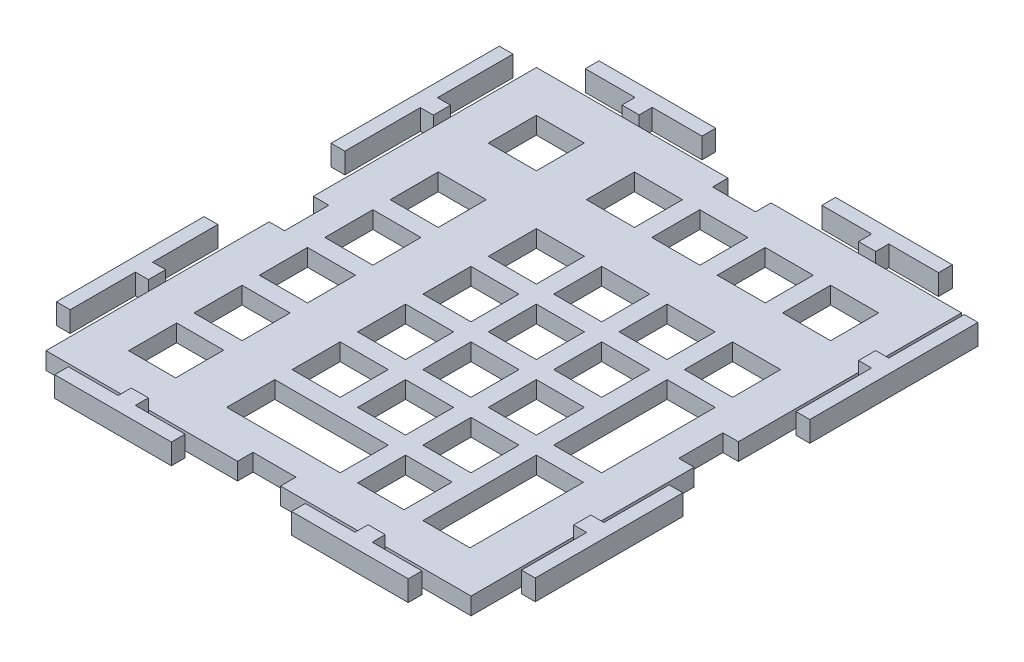
SolidWorks part; units mm, degrees
ref_plane "Front Plane" through (0, 0, 0) normal (0, 0, 1) x (1, 0, 0)
ref_plane "Top Plane" through (0, 0, 0) normal (0, 1, 0) x (1, 0, 0)
ref_plane "Right Plane" through (0, 0, 0) normal (1, 0, 0) x (0, 0, -1)
sketch "Sketch2" plane through (0, 0, 0) normal (0, 1, 0) x (1, 0, 0)
  line L0 (-50.856, -62.0444) -> (43.049, -62.0444)
  line L1 (-65.816, -47.0844) -> (-65.816, 65.8706)
  line L2 (-50.856, 80.8306) -> (43.049, 80.8306)
  line L3 (58.009, -47.0844) -> (58.009, 65.8706)
  line L4 (-65.816, -62.0444) -> (58.009, 80.8306) construction
  line L5 (-65.816, 80.8306) -> (58.009, -62.0444) construction
  line L6 (31.959, 54.7456) -> (45.959, 54.7456)
  line L7 (31.959, 54.7456) -> (31.959, 68.7456)
  line L8 (31.959, 68.7456) -> (45.959, 68.7456)
  line L9 (45.959, 54.7456) -> (45.959, 68.7456)
  line L10 (31.959, 54.7456) -> (45.959, 68.7456) construction
  line L11 (31.959, 68.7456) -> (45.959, 54.7456) construction
  line L12 (31.959, 61.7456) -> (26.909, 61.7456) construction
  line L13 (12.909, 54.7456) -> (26.909, 54.7456)
  line L14 (12.909, 54.7456) -> (12.909, 68.7456)
  line L15 (12.909, 68.7456) -> (26.909, 68.7456)
  line L16 (26.909, 54.7456) -> (26.909, 68.7456)
  line L17 (12.909, 61.7456) -> (7.859, 61.7456) construction
  line L18 (-6.141, 54.7456) -> (7.859, 54.7456)
  line L19 (-6.141, 54.7456) -> (-6.141, 68.7456)
  line L20 (-6.141, 68.7456) -> (7.859, 68.7456)
  line L21 (7.859, 54.7456) -> (7.859, 68.7456)
  line L22 (-6.141, 61.7456) -> (-11.191, 61.7456) construction
  line L23 (-25.191, 54.7456) -> (-11.191, 54.7456)
  line L24 (-25.191, 54.7456) -> (-25.191, 68.7456)
  line L25 (-25.191, 68.7456) -> (-11.191, 68.7456)
  line L26 (-11.191, 54.7456) -> (-11.191, 68.7456)
  line L27 (31.959, 26.1706) -> (45.959, 26.1706)
  line L28 (-53.766, 54.7456) -> (-39.766, 54.7456)
  line L29 (-53.766, 54.7456) -> (-53.766, 68.7456)
  line L30 (-53.766, 68.7456) -> (-39.766, 68.7456)
  line L31 (-39.766, 54.7456) -> (-39.766, 68.7456)
  line L32 (31.959, 26.1706) -> (31.959, 40.1706)
  line L33 (31.959, 40.1706) -> (45.959, 40.1706)
  line L34 (45.959, 26.1706) -> (45.959, 40.1706)
  line L35 (31.959, 26.1706) -> (45.959, 40.1706) construction
  line L36 (31.959, 40.1706) -> (45.959, 26.1706) construction
  line L37 (31.959, 33.1706) -> (26.909, 33.1706) construction
  line L38 (12.909, 26.1706) -> (26.909, 26.1706)
  line L39 (12.909, 26.1706) -> (12.909, 40.1706)
  line L40 (12.909, 40.1706) -> (26.909, 40.1706)
  line L41 (26.909, 26.1706) -> (26.909, 40.1706)
  line L42 (12.909, 33.1706) -> (7.859, 33.1706) construction
  line L43 (-6.141, 26.1706) -> (7.859, 26.1706)
  line L44 (-6.141, 26.1706) -> (-6.141, 40.1706)
  line L45 (-6.141, 40.1706) -> (7.859, 40.1706)
  line L46 (7.859, 26.1706) -> (7.859, 40.1706)
  line L47 (-6.141, 33.1706) -> (-11.191, 33.1706) construction
  line L48 (-25.191, 26.1706) -> (-11.191, 26.1706)
  line L49 (-25.191, 26.1706) -> (-25.191, 40.1706)
  line L50 (-25.191, 40.1706) -> (-11.191, 40.1706)
  line L51 (-11.191, 26.1706) -> (-11.191, 40.1706)
  line L52 (-53.766, 26.1706) -> (-39.766, 26.1706)
  line L53 (-53.766, 26.1706) -> (-53.766, 40.1706)
  line L54 (-53.766, 40.1706) -> (-39.766, 40.1706)
  line L55 (-39.766, 26.1706) -> (-39.766, 40.1706)
  line L56 (31.959, -11.9294) -> (45.959, -11.9294)
  line L57 (31.959, -11.9294) -> (31.959, 21.1206)
  line L58 (31.959, 21.1206) -> (45.959, 21.1206)
  line L59 (45.959, -11.9294) -> (45.959, 21.1206)
  line L60 (31.959, -11.9294) -> (45.959, 21.1206) construction
  line L61 (31.959, 21.1206) -> (45.959, -11.9294) construction
  line L62 (31.959, 4.5956) -> (26.909, 4.5956) construction
  line L63 (12.909, 7.1206) -> (26.909, 7.1206)
  line L64 (12.909, 7.1206) -> (12.909, 21.1206)
  line L65 (12.909, 21.1206) -> (26.909, 21.1206)
  line L66 (26.909, 7.1206) -> (26.909, 21.1206)
  line L67 (12.909, 14.1206) -> (7.859, 14.1206) construction
  line L68 (-6.141, 7.1206) -> (7.859, 7.1206)
  line L69 (-6.141, 7.1206) -> (-6.141, 21.1206)
  line L70 (-6.141, 21.1206) -> (7.859, 21.1206)
  line L71 (7.859, 7.1206) -> (7.859, 21.1206)
  line L72 (-6.141, 14.1206) -> (-11.191, 14.1206) construction
  line L73 (-25.191, 7.1206) -> (-11.191, 7.1206)
  line L74 (-25.191, 7.1206) -> (-25.191, 21.1206)
  line L75 (-25.191, 21.1206) -> (-11.191, 21.1206)
  line L76 (-11.191, 7.1206) -> (-11.191, 21.1206)
  line L77 (-53.766, 7.1206) -> (-39.766, 7.1206)
  line L78 (-53.766, 7.1206) -> (-53.766, 21.1206)
  line L79 (-53.766, 21.1206) -> (-39.766, 21.1206)
  line L80 (-39.766, 7.1206) -> (-39.766, 21.1206)
  line L85 (-65.816, 65.8706) -> (-65.816, 80.8306)
  line L88 (12.909, -11.9294) -> (26.909, -11.9294)
  line L89 (12.909, -11.9294) -> (12.909, 2.0706)
  line L90 (12.909, 2.0706) -> (26.909, 2.0706)
  line L91 (26.909, -11.9294) -> (26.909, 2.0706)
  line L92 (12.909, -4.9294) -> (7.859, -4.9294) construction
  line L93 (-6.141, -11.9294) -> (7.859, -11.9294)
  line L94 (-6.141, -11.9294) -> (-6.141, 2.0706)
  line L95 (-6.141, 2.0706) -> (7.859, 2.0706)
  line L96 (7.859, -11.9294) -> (7.859, 2.0706)
  line L97 (-6.141, -4.9294) -> (-11.191, -4.9294) construction
  line L98 (-25.191, -11.9294) -> (-11.191, -11.9294)
  line L99 (-25.191, -11.9294) -> (-25.191, 2.0706)
  line L100 (-25.191, 2.0706) -> (-11.191, 2.0706)
  line L101 (-11.191, -11.9294) -> (-11.191, 2.0706)
  line L102 (-53.766, -11.9294) -> (-39.766, -11.9294)
  line L103 (-53.766, -11.9294) -> (-53.766, 2.0706)
  line L104 (-53.766, 2.0706) -> (-39.766, 2.0706)
  line L105 (-39.766, -11.9294) -> (-39.766, 2.0706)
  line L112 (31.959, -50.0294) -> (45.6886, -50.0294)
  line L113 (12.909, -30.9794) -> (26.909, -30.9794)
  line L114 (12.909, -30.9794) -> (12.909, -16.9794)
  line L115 (12.909, -16.9794) -> (26.909, -16.9794)
  line L116 (26.909, -30.9794) -> (26.909, -16.9794)
  line L117 (12.909, -23.9794) -> (7.859, -23.9794) construction
  line L118 (-6.141, -30.9794) -> (7.859, -30.9794)
  line L119 (-6.141, -30.9794) -> (-6.141, -16.9794)
  line L120 (-6.141, -16.9794) -> (7.859, -16.9794)
  line L121 (7.859, -30.9794) -> (7.859, -16.9794)
  line L122 (-6.141, -23.9794) -> (-11.191, -23.9794) construction
  line L123 (-25.191, -30.9794) -> (-11.191, -30.9794)
  line L124 (-25.191, -30.9794) -> (-25.191, -16.9794)
  line L125 (-25.191, -16.9794) -> (-11.191, -16.9794)
  line L126 (-11.191, -30.9794) -> (-11.191, -16.9794)
  line L127 (-53.766, -30.9794) -> (-39.766, -30.9794)
  line L128 (-53.766, -30.9794) -> (-53.766, -16.9794)
  line L129 (-53.766, -16.9794) -> (-39.766, -16.9794)
  line L130 (-39.766, -30.9794) -> (-39.766, -16.9794)
  line L131 (-53.766, -50.0294) -> (-40.0588, -50.0294)
  line L132 (-53.766, -50.0294) -> (-53.766, -36.0294)
  line L133 (-53.766, -36.0294) -> (-40.0588, -36.0294)
  line L134 (-40.0588, -50.0294) -> (-40.0588, -36.0294)
  line L135 (-25.191, -50.0294) -> (7.859, -50.0294)
  line L136 (-25.191, -50.0294) -> (-25.191, -36.0294)
  line L137 (-25.191, -36.0294) -> (7.859, -36.0294)
  line L138 (7.859, -50.0294) -> (7.859, -36.0294)
  line L139 (12.909, -50.0294) -> (26.4811, -50.0294)
  line L140 (12.909, -50.0294) -> (12.909, -36.0294)
  line L141 (12.909, -36.0294) -> (26.4811, -36.0294)
  line L142 (26.4811, -50.0294) -> (26.4811, -36.0294)
  line L143 (31.959, -50.0294) -> (31.959, -16.9794)
  line L144 (31.959, -16.9794) -> (45.6886, -16.9794)
  line L145 (45.6886, -50.0294) -> (45.6886, -16.9794)
  line L146 (-65.816, 80.8306) -> (-50.856, 80.8306)
  line L147 (43.049, 80.8306) -> (58.009, 80.8306)
  line L148 (58.009, 80.8306) -> (58.009, 65.8706)
  line L149 (58.009, -47.0844) -> (58.009, -62.0444)
  line L150 (58.009, -62.0444) -> (43.049, -62.0444)
  line L151 (-50.856, -62.0444) -> (-65.816, -62.0444)
  line L152 (-65.816, -62.0444) -> (-65.816, -47.0844)
  point P0 (-3.9035, 9.3931)
  point P17 (38.959, 61.7456)
  point P40 (38.959, 33.1706)
  point P72 (-1.0487, -8.3316)
  point P73 (38.959, 4.5956)
  point P100 (-3.9035, -35.5277)
  dimension "D1" = 123.825
  dimension "D2" = 142.875
  dimension "D3" = 14
  dimension "D4" = 14
  dimension "D5" = 5.05
  dimension "D6" = 5.05
  dimension "D7" = 5.05
  dimension "D8" = 14
  dimension "D9" = 14
  dimension "D10" = 14
  dimension "D11" = 14
  dimension "D12" = 14.575
  dimension "D13" = 14
  dimension "D14" = 14
  dimension "D15" = 5.05
  dimension "D16" = 5.05
  dimension "D17" = 5.05
  dimension "D18" = 14
  dimension "D19" = 14
  dimension "D20" = 14
  dimension "D21" = 14
  dimension "D22" = 12.085
  dimension "D23" = 12.05
  dimension "D24" = 14
  dimension "D25" = 14
  dimension "D26" = 14
  dimension "D27" = 14
  dimension "D28" = 14.575
  dimension "D29" = 14
  dimension "D30" = 14
  dimension "D31" = 14
  dimension "D32" = 14
  dimension "D33" = 14.575
  dimension "D34" = 14
  dimension "D35" = 33.05
  dimension "D36" = 5.05
  dimension "D37" = 5.05
  dimension "D38" = 5.05
  dimension "D39" = 14
  dimension "D40" = 14
  dimension "D41" = 14
  dimension "D42" = 14
  dimension "D43" = 14.575
  dimension "D44" = 14
  dimension "D45" = 14
  dimension "D46" = 14
  dimension "D47" = 14
  dimension "D48" = 5.05
  dimension "D49" = 33.05
  dimension "D50" = 5.05
  dimension "D51" = 5.05
  dimension "D52" = 5.05
  dimension "D53" = 5.05
  dimension "D54" = 14
  dimension "D55" = 14
  dimension "D56" = 14
  dimension "D57" = 14
  dimension "D58" = 14.575
  dimension "D59" = 14
  dimension "D60" = 14
  dimension "D61" = 14
  dimension "D62" = 14
  dimension "D66" = 5.05
  dimension "D67" = 5.05
  dimension "D68" = 14
  dimension "D69" = 14
  dimension "D70" = 14
  dimension "D71" = 14
  dimension "D72" = 5.05
  dimension "D73" = 5.05
  dimension "D74" = 14
  dimension "D75" = 5.05
  dimension "D76" = 14
  dimension "D77" = 14.575
  dimension "D78" = 14
  dimension "D79" = 33.05
  dimension "D80" = 5.05
extrude "Boss-Extrude1" add sketch "Sketch2" along normal blind 5
sketch "Sketch4" plane through (0, 5, 0) normal (0, 1, 0) x (1, 0, 0)
  line L0 (-3.9035, 87.6298) -> (-3.9035, -67.0539) construction
  line L1 (-68.78, 9.3931) -> (60.0523, 9.3931) construction
  line L2 (58.009, 80.8306) -> (2.509, 80.8306) construction
  line L3 (58.009, 80.8306) -> (-65.816, 80.8306) construction
  line L4 (-65.816, 80.8306) -> (-10.016, 80.8306) construction
  line L5 (-10.016, 80.8306) -> (-10.016, 76.3306)
  line L6 (-10.016, 76.3306) -> (2.509, 76.3306)
  line L7 (2.509, 76.3306) -> (2.509, 80.8306)
  line L8 (2.509, 80.8306) -> (-10.016, 80.8306)
  line L9 (58.009, -62.0444) -> (2.509, -62.0444) construction
  line L10 (-65.816, -62.0444) -> (58.009, -62.0444) construction
  line L11 (2.509, -62.0444) -> (2.509, -57.5444)
  line L12 (2.509, -57.5444) -> (-10.016, -57.5444)
  line L13 (-10.016, -57.5444) -> (-10.016, -62.0444)
  line L14 (-10.016, -62.0444) -> (2.509, -62.0444)
  line L15 (58.009, 80.8306) -> (58.009, 15.8306) construction
  line L16 (58.009, -62.0444) -> (58.009, 80.8306) construction
  line L17 (58.009, 15.8306) -> (53.509, 15.8306)
  line L18 (58.009, -62.0444) -> (58.009, 2.9556) construction
  line L19 (53.509, 15.8306) -> (53.509, 2.9556)
  line L20 (53.509, 2.9556) -> (58.009, 2.9556)
  line L21 (58.009, 2.9556) -> (58.009, 15.8306)
  line L22 (-65.816, 15.8306) -> (-61.316, 15.8306)
  line L23 (-65.816, 80.8306) -> (-65.816, -62.0444) construction
  line L24 (-61.316, 15.8306) -> (-61.316, 2.9556)
  line L25 (-61.316, 2.9556) -> (-65.816, 2.9556)
  line L26 (-65.816, 2.9556) -> (-65.816, 15.8306)
  dimension "D1" = 55.8
  dimension "55.5" = 55.5
  dimension "D2" = 4.5
  dimension "D3" = 4.5
  dimension "D4" = 65
  dimension "D5" = 4.5
  dimension "D6" = 65
  dimension "D7" = 4.5
extrude "Cut-Extrude1" cut sketch "Sketch4" against normal through all
sketch "Sketch5" plane through (0, 5, 0) normal (0, 1, 0) x (1, 0, 0)
  line L0 (-35.8975, 80.8306) -> (-40.8975, 80.8306)
  line L1 (-69.616, 55.8022) -> (-65.816, 55.8022)
  line L2 (28.009, -62.0444) -> (33.009, -62.0444)
  line L3 (-35.8975, 80.8306) -> (-35.8975, 84.6306)
  line L4 (-35.8975, 84.6306) -> (-21.3975, 84.6306)
  line L5 (-21.3975, 84.6306) -> (-21.3975, 88.6306)
  line L6 (-40.8975, 80.8306) -> (-40.8975, 84.6306)
  line L7 (-40.8975, 84.6306) -> (-55.3975, 84.6306)
  line L8 (-55.3975, 84.6306) -> (-55.3975, 88.6306)
  line L9 (-55.3975, 88.6306) -> (-21.3975, 88.6306)
  line L12 (33.0168, 84.6306) -> (47.5168, 84.6306)
  line L13 (47.5168, 84.6306) -> (47.5168, 88.6306)
  line L15 (28.0168, 84.6306) -> (13.5168, 84.6306)
  line L16 (13.5168, 84.6306) -> (13.5168, 88.6306)
  line L17 (13.5168, 88.6306) -> (47.5168, 88.6306)
  line L19 (58.009, -62.0444) -> (30.509, -62.0444) construction
  line L20 (2.509, -62.0444) -> (58.009, -62.0444) construction
  line L22 (-35.9908, -65.8444) -> (-21.4908, -65.8444)
  line L24 (-40.9908, -65.8444) -> (-55.4908, -65.8444)
  line L25 (-21.4908, -65.8444) -> (-21.4908, -69.8444)
  line L26 (-55.4908, -65.8444) -> (-55.4908, -69.8444)
  line L27 (-55.4908, -69.8444) -> (-21.4908, -69.8444)
  line L29 (33.009, -62.0444) -> (33.009, -65.8444)
  line L30 (33.009, -65.8444) -> (47.509, -65.8444)
  line L31 (28.009, -62.0444) -> (28.009, -65.8444)
  line L32 (28.009, -65.8444) -> (13.509, -65.8444)
  line L33 (47.509, -65.8444) -> (47.509, -69.8444)
  line L34 (13.509, -65.8444) -> (13.509, -69.8444)
  line L35 (13.509, -69.8444) -> (47.509, -69.8444)
  line L37 (-41.3975, 80.8306) -> (-35.3975, 80.8306) construction
  line L38 (-10.016, 80.8306) -> (-65.816, 80.8306) construction
  line L41 (-69.616, 50.8022) -> (-69.616, 28.8022)
  line L42 (-69.616, 28.8022) -> (-73.616, 28.8022)
  line L43 (-69.616, 55.8022) -> (-69.616, 77.8022)
  line L44 (-69.616, 77.8022) -> (-73.616, 77.8022)
  line L45 (-73.616, 77.8022) -> (-73.616, 28.8022)
  line L47 (-65.816, -27.1978) -> (-69.616, -27.1978)
  line L48 (-65.816, -32.1978) -> (-69.616, -32.1978)
  line L49 (-69.616, -32.1978) -> (-69.616, -51.1978)
  line L50 (-69.616, -51.1978) -> (-73.616, -51.1978)
  line L51 (-69.616, -27.1978) -> (-69.616, -8.1978)
  line L52 (-69.616, -8.1978) -> (-73.616, -8.1978)
  line L53 (-73.616, -8.1978) -> (-73.616, -51.1978)
  line L58 (61.809, 55.8306) -> (61.809, 77.8306)
  line L59 (61.809, 77.8306) -> (65.809, 77.8306)
  line L60 (61.809, 50.8306) -> (61.809, 28.8306)
  line L61 (61.809, 28.8306) -> (65.809, 28.8306)
  line L62 (65.809, 77.8306) -> (65.809, 28.8306)
  line L64 (58.009, -27.1444) -> (61.809, -27.1444)
  line L65 (58.009, -32.1444) -> (61.809, -32.1444)
  line L66 (61.809, -27.1444) -> (61.809, -8.1444)
  line L67 (61.809, -8.1444) -> (65.809, -8.1444)
  line L68 (61.809, -32.1444) -> (61.809, -51.1444)
  line L69 (61.809, -51.1444) -> (65.809, -51.1444)
  line L70 (65.809, -8.1444) -> (65.809, -51.1444)
  line L71 (27.5168, 80.8306) -> (33.5168, 80.8306) construction
  line L72 (-65.816, 55.8022) -> (-65.816, 50.8022)
  line L73 (-65.816, 50.8022) -> (-69.616, 50.8022)
  line L74 (-65.816, -62.0444) -> (-65.816, -29.6978) construction
  line L75 (58.009, 80.8306) -> (58.009, 53.3306) construction
  line L76 (58.009, 15.8306) -> (58.009, 80.8306) construction
  line L77 (61.809, 50.8306) -> (58.009, 50.8306)
  line L78 (28.0168, 84.6306) -> (28.0168, 80.8306)
  line L79 (28.0168, 80.8306) -> (33.0168, 80.8306)
  line L80 (33.0168, 80.8306) -> (33.0168, 84.6306)
  line L81 (58.009, 80.8306) -> (2.509, 80.8306) construction
  line L82 (58.009, 50.8306) -> (58.009, 55.8306)
  line L83 (58.009, -62.0444) -> (58.009, -29.6444) construction
  line L84 (58.009, 55.8306) -> (61.809, 55.8306)
  line L85 (-65.816, -27.1978) -> (-65.816, -32.1978)
  line L86 (-40.9908, -65.8444) -> (-40.9908, -62.0444)
  line L87 (-40.9908, -62.0444) -> (-35.9908, -62.0444)
  line L88 (-35.9908, -62.0444) -> (-35.9908, -65.8444)
  line L89 (-66.4832, -62.6978) -> (-38.4908, -62.0444) construction
  line L90 (-65.816, -62.0444) -> (-10.016, -62.0444) construction
  line L91 (-65.816, 80.8306) -> (-65.816, 53.3022) construction
  line L92 (-65.816, 80.8306) -> (-65.816, 15.8306) construction
  line L93 (-65.816, 2.9556) -> (-65.816, -62.0444) construction
  line L94 (58.009, -62.0444) -> (58.009, 2.9556) construction
  line L95 (58.009, -27.1444) -> (58.009, -32.1444)
  point P6 (-38.3975, 80.8306)
  point P26 (-38.4908, -62.0444)
  point P51 (-65.816, 53.3022)
  point P52 (30.5168, 80.8306)
  point P53 (-38.3975, 80.8306)
  point P71 (30.509, -62.0444)
  point P74 (58.009, 53.3306)
  point P86 (58.009, -29.6444)
  point P103 (-65.816, -29.6978)
  point P105 (30.5168, 80.8306)
  dimension "D1" = 5
  dimension "D2" = 3.8
  dimension "D3" = 14.5
  dimension "D4" = 4
  dimension "D5" = 3.8
  dimension "D6" = 5
  dimension "D7" = 14.5
  dimension "D8" = 4
  dimension "D9" = 5
  dimension "D10" = 3.8
  dimension "D11" = 14.5
  dimension "D12" = 4
  dimension "D13" = 5
  dimension "D14" = 3.8
  dimension "D15" = 14.5
  dimension "D16" = 4
  dimension "D17" = 3.8
  dimension "D18" = 5
  dimension "D19" = 22
  dimension "D20" = 4
  dimension "D21" = 5
  dimension "D22" = 3.8
  dimension "D23" = 19
  dimension "D24" = 4
  dimension "D25" = 27.5
  dimension "D26" = 5
  dimension "D27" = 22
  dimension "D28" = 4
  dimension "D29" = 5
  dimension "D30" = 3.8
  dimension "D31" = 19
  dimension "D32" = 4
  dimension "D33" = 28
  dimension "D34" = 27.5
  dimension "D35" = 6
  dimension "D36" = 6
  dimension "D37" = 0
  dimension "D38" = 32.4
  dimension "D39" = 3.8
extrude "Boss-Extrude2" add sketch "Sketch5" along normal mid plane 6
